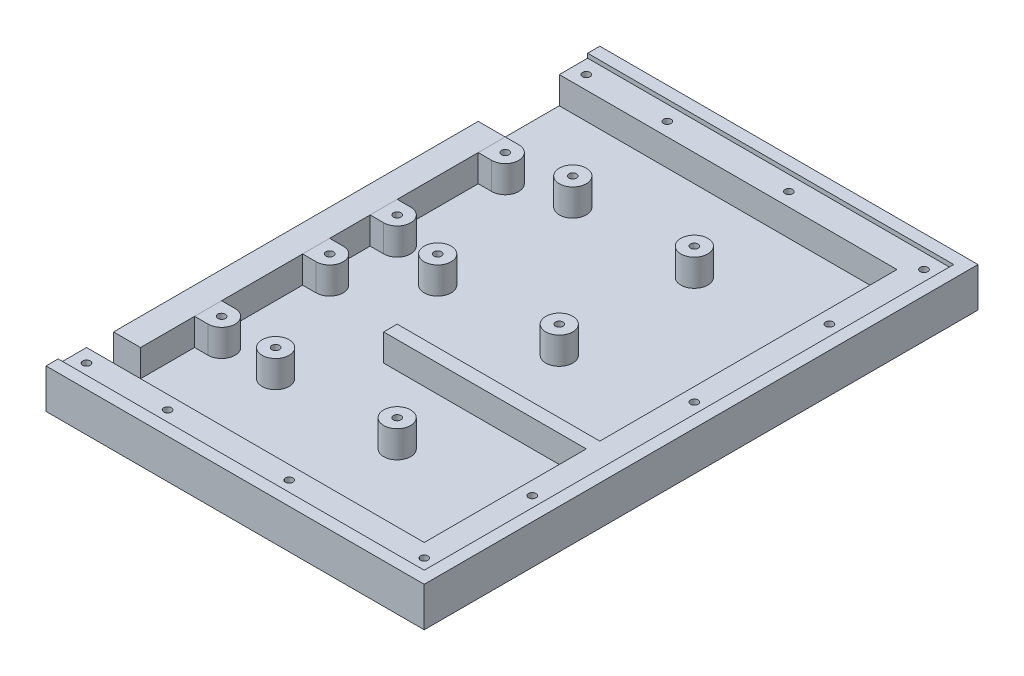
SolidWorks part; units mm, degrees
ref_plane "Front Plane" through (0, 0, 0) normal (0, 0, 1) x (1, 0, 0)
ref_plane "Top Plane" through (0, 0, 0) normal (0, 1, 0) x (1, 0, 0)
ref_plane "Right Plane" through (0, 0, 0) normal (1, 0, 0) x (0, 0, -1)
sketch "Sketch1" plane through (0, 0, 0) normal (0, 1, 0) x (1, 0, 0)
  line L1 (0, 0) -> (135, 0) construction
  line L2 (0, 0) -> (0, -195) construction
  line L3 (0, -195) -> (135, -195) construction
  line L4 (135, 0) -> (135, -195) construction
  line L8 (-0.5, 0.5) -> (-0.5, -195.5)
  line L9 (-0.5, -195.5) -> (135.5, -195.5)
  line L10 (135.5, 0.5) -> (135.5, -195.5)
  line L11 (-0.5, 0.5) -> (135.5, 0.5)
  line L13 (140, -200) -> (0, -200)
  line L14 (140, -200) -> (140, 5)
  line L15 (140, 5) -> (0, 5)
  line L16 (0, -200) -> (0, 5)
  dimension "D1" = 135
  dimension "D2" = 195
  dimension "D5" = 5
  dimension "D3" = 5
  dimension "D6" = 5
  dimension "D7" = 0
  dimension "D4" = 0.5
extrude "Boss-Extrude1" add sketch "Sketch1" along normal blind 1.6 contours L16 L13 L14 L15 L11 L10 L9 region at (2.4824, 0, -2.75)
sketch "Sketch2" plane through (0, 0, 0) normal (0, 1, 0) x (1, 0, 0)
  line L8 (0, 0) -> (135, 0) construction
  line L9 (10, -10) -> (125, -10)
  line L10 (10, -10) -> (10, -185)
  line L11 (10, -185) -> (125, -185)
  line L12 (125, -10) -> (125, -185)
  line L14 (0, -195) -> (135, -195) construction
  line L15 (0, 0) -> (0, -195) construction
  line L16 (-0.5, 0.5) -> (-0.5, -195.5) construction
  line L17 (140, 5) -> (0, 5)
  line L18 (140, 5) -> (140, -200)
  line L19 (140, -200) -> (0, -200)
  line L20 (0, 5) -> (0, -200)
  line L21 (-4.176, -185) -> (19.5, -185)
  line L22 (-4.176, -185) -> (-4.176, -175)
  line L23 (-4.176, -175) -> (19.5, -175)
  line L24 (19.5, -185) -> (19.5, -175)
  line L26 (-7.239, -10) -> (14.5, -10)
  line L27 (-7.239, -10) -> (-7.239, -40)
  line L28 (-7.239, -40) -> (14.5, -40)
  line L29 (14.5, -10) -> (14.5, -40)
  line L30 (129.7056, -120) -> (50, -120)
  line L31 (129.7056, -120) -> (129.7056, -125)
  line L32 (129.7056, -125) -> (50, -125)
  line L33 (50, -120) -> (50, -125)
  dimension "D1" = 10
  dimension "D2" = 10
  dimension "D3" = 10
  dimension "D4" = 10
  dimension "D5" = 10
  dimension "D6" = 20
  dimension "D7" = 10
  dimension "D8" = 30
  dimension "D9" = 15
  dimension "D10" = 70
  dimension "D11" = 5
  dimension "D12" = 50
extrude "Boss-Extrude2" add sketch "Sketch2" against normal blind 10 contours L31 L32 L12 L11 L21 L20 L19 L18 L17 L26 L9 L30 | L28 L20 L23 L10 | L30 L33 L32 L12 | L32 L31 L30 L12 region at (5, 0, 7.5176) region at (5, 0, 107.5) region at (127.3528, 0, 122.5) region at (87.5, 0, 122.5)
sketch "Sketch3" plane through (0, -10, 0) normal (0, -1, 0) x (1, 0, 0)
  line L1 (0, 200) -> (140, 200)
  line L2 (0, 200) -> (0, -5)
  line L3 (0, -5) -> (140, -5)
  line L4 (140, 200) -> (140, -5)
extrude "Boss-Extrude3" add sketch "Sketch3" along normal blind 3
sketch "Sketch4" plane through (0, 0, 0) normal (0, 1, 0) x (1, 0, 0)
  line L0 (0, 0) -> (135, 0) construction
  line L1 (0, -200) -> (0, 5) construction
  line L2 (135, 0) -> (135, -195) construction
  line L3 (0, -195) -> (135, -195) construction
  circle A0 centre (5, -5) radius 1.4
  circle A1 centre (35, -5) radius 1.4
  circle A2 centre (80, -5) radius 1.4
  circle A3 centre (130, -5) radius 1.4
  circle A4 centre (5, -190) radius 1.4
  circle A5 centre (35, -190) radius 1.4
  circle A6 centre (80, -190) radius 1.4
  circle A7 centre (130, -190) radius 1.4
  circle A8 centre (130, -40) radius 1.4
  circle A9 centre (130, -150) radius 1.4
  circle A10 centre (130, -90) radius 1.4
  dimension "D1" = 5
  dimension "D3" = 30
  dimension "D4" = 5
  dimension "D6" = 5
  dimension "D7" = 35
  dimension "D2" = 5
  dimension "D5" = 45
  dimension "D8" = 40
  dimension "D9" = 50
extrude "Cut-Extrude1" cut sketch "Sketch4" against normal blind 10
sketch "Sketch5" plane through (0, 0, 0) normal (0, 1, 0) x (1, 0, 0)
  line L0 (0, -200) -> (0, 5) construction
  line L1 (0, 0) -> (135, 0) construction
  line L3 (10, -40) -> (10, -175) construction
  line L4 (15, -40) -> (10, -40)
  line L5 (15, -40) -> (15, -50)
  line L6 (15, -50) -> (10, -50)
  line L7 (10, -40) -> (10, -50)
  line L8 (10, -40) -> (10, -175) construction
  line L9 (15, -80) -> (10, -80)
  line L10 (15, -80) -> (15, -90)
  line L11 (15, -90) -> (10, -90)
  line L12 (10, -80) -> (10, -90)
  line L14 (15, -115) -> (10, -115)
  line L15 (15, -115) -> (15, -105)
  line L16 (15, -105) -> (10, -105)
  line L17 (10, -115) -> (10, -105)
  line L18 (15, -155) -> (10, -155)
  line L19 (15, -155) -> (15, -145)
  line L20 (15, -145) -> (10, -145)
  line L21 (10, -155) -> (10, -145)
  circle A0 centre (35, -40) radius 1.4
  circle A2 centre (35, -5) radius 1.4 construction
  circle A3 centre (130, -40) radius 1.4 construction
  circle A4 centre (80, -40) radius 1.4
  circle A5 centre (80, -5) radius 1.4 construction
  circle A6 centre (35, -90) radius 1.4
  circle A7 centre (130, -90) radius 1.4 construction
  circle A8 centre (80, -90) radius 1.4
  circle A9 centre (35, -150) radius 1.4
  circle A10 centre (130, -150) radius 1.4 construction
  circle A11 centre (80, -150) radius 1.4
  circle A12 centre (15, -45) radius 1.4
  circle A13 centre (15, -85) radius 1.4
  circle A14 centre (15, -150) radius 1.4
  circle A15 centre (15, -110) radius 1.4
  circle A16 centre (35, -40) radius 5
  circle A17 centre (80, -40) radius 5
  circle A18 centre (15, -85) radius 5
  circle A19 centre (15, -45) radius 5
  circle A20 centre (15, -110) radius 5
  circle A21 centre (35, -90) radius 5
  circle A22 centre (80, -90) radius 5
  circle A23 centre (80, -150) radius 5
  circle A24 centre (35, -150) radius 5
  circle A25 centre (15, -150) radius 5
  dimension "D1" = 0
  dimension "D2" = 0
  dimension "D3" = 0
  dimension "D4" = 0
  dimension "D5" = 0
  dimension "D6" = 15
  dimension "D8" = 5
  dimension "D9" = 40
  dimension "D7" = 45
  dimension "D10" = 15
  dimension "D11" = 15
extrude "Boss-Extrude4" add sketch "Sketch5" against normal up to surface (10 mm away) separate body contours A22 A8 | A17 A4 | A16 A0 | A21 A6 | A24 A9 | A23 A11 | A19 L4 L7 | L5 A19 A12 | A19 L7 L6 | L5 A19 A12 | A25 L21 L18 | L19 A25 A14 | L19 A25 A14 | A25 L20 L21 | L10 A18 A13 | L10 A18 A13 | A18 L12 L11 | A18 L9 L12 | A20 L16 L17 | L15 A20 A15 | A20 L17 L14 | L15 A20 A15 region at (11.1168, 0, 41.1168) region at (17.252, 0, 45) region at (12.748, 0, 45) region at (11.1168, 0, 48.8832) region at (11.1168, 0, 81.1168) region at (17.252, 0, 85) region at (12.748, 0, 85) region at (11.1168, 0, 88.8832) region at (12.748, 0, 110) region at (17.252, 0, 110) region at (11.1168, 0, 113.8832) region at (11.1168, 0, 106.1168) region at (12.748, 0, 150) region at (17.252, 0, 150) region at (11.1168, 0, 153.8832) region at (11.1168, 0, 146.1168) region at (30.1414, 0, 40) region at (75.1414, 0, 40) region at (30.1414, 0, 90) region at (75.1414, 0, 90) region at (75.1414, 0, 150) region at (30.1414, 0, 150) up to face at (51.6667, -10, 109.1667)
